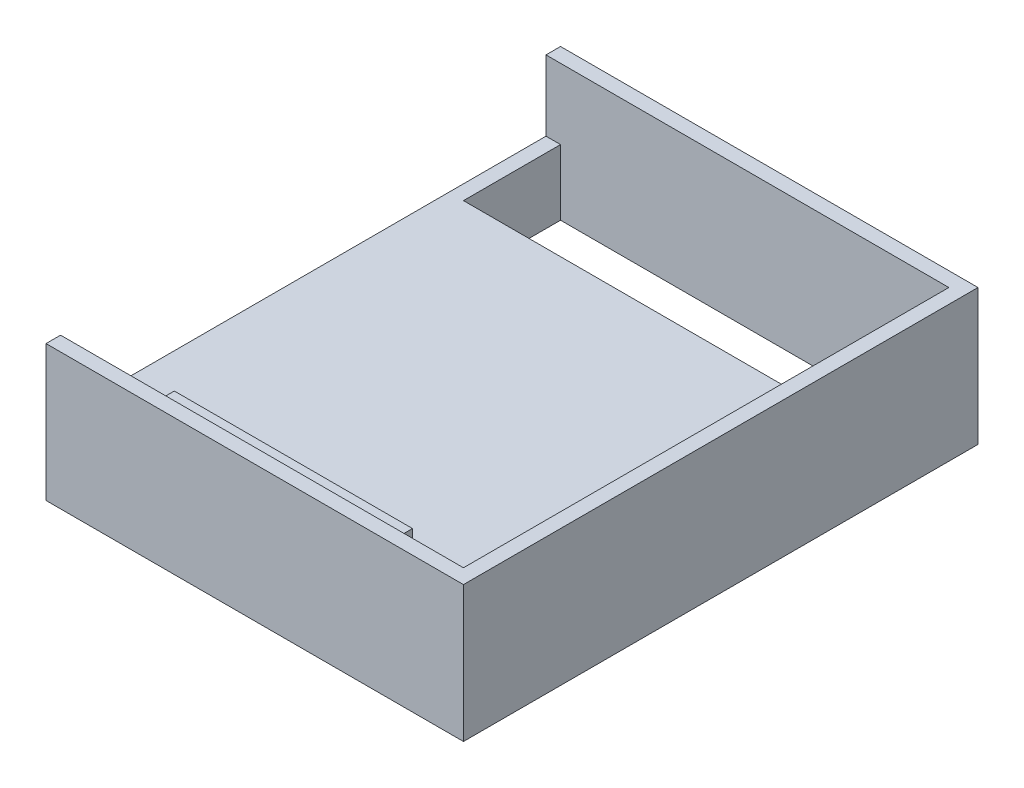
SolidWorks part; units mm, degrees
ref_plane "前视基准面" through (0, 0, 0) normal (0, 0, 1) x (1, 0, 0)
ref_plane "上视基准面" through (0, 0, 0) normal (0, 1, 0) x (1, 0, 0)
ref_plane "右视基准面" through (0, 0, 0) normal (1, 0, 0) x (0, 0, -1)
other "Configuration Table"
sketch "草图1" plane through (0, 0, 0) normal (0, 1, 0) x (1, 0, 0)
  line L0 (0, 0) -> (0, 42.4)
  line L1 (0, 42.4) -> (34.4, 42.4)
  line L2 (34.4, 0) -> (0, 0)
  line L3 (34.4, 42.4) -> (34.4, 0)
extrude "凸台-拉伸1" add sketch "草图1" along normal blind 7
sketch "草图2" plane through (0, 7, 0) normal (0, 1, 0) x (1, 0, 0)
  line L1 (0, 41.2) -> (33.2, 41.2)
  line L2 (33.2, 41.2) -> (33.2, 1.2)
  line L3 (33.2, 1.2) -> (0, 1.2)
  line L4 (0, 41.2) -> (0, 1.2)
extrude "切除-拉伸1" cut sketch "草图2" against normal blind 5.8
sketch "草图3" plane through (0, 0, 0) normal (0, -1, 0) x (1, 0, 0)
  line L1 (0, 0) -> (34.4, 0)
  line L2 (0, 0) -> (0, -42.4)
  line L3 (0, -42.4) -> (34.4, -42.4)
  line L4 (34.4, 0) -> (34.4, -42.4)
extrude "凸台-拉伸2" add sketch "草图3" along normal blind 4.2
sketch "草图4" plane through (0, -4.2, 0) normal (0, -1, 0) x (1, 0, 0)
  line L0 (1.2, -1.2) -> (1.2, -41.2)
  line L1 (1.2, -1.2) -> (33.2, -1.2)
  line L2 (33.2, -1.2) -> (33.2, -41.2)
  line L3 (33.2, -41.2) -> (1.2, -41.2)
extrude "切除-拉伸2" cut sketch "草图4" against normal blind 4.2
sketch "草图5" plane through (0, 0, 0) normal (0, -1, 0) x (1, 0, 0)
  line L0 (1.2, -41.2) -> (33.2, -41.2)
  line L1 (33.2, -41.2) -> (33.2, -33.2)
  line L2 (33.2, -41.2) -> (33.2, -1.2) construction
  line L3 (33.2, -33.2) -> (1.2, -33.2)
  line L4 (1.2, -1.2) -> (1.2, -41.2) construction
  line L5 (1.2, -33.2) -> (1.2, -41.2)
extrude "切除-拉伸-穿线孔" cut sketch "草图5" against normal blind 1.2
sketch "草图6" plane through (0, 1.2, 0) normal (0, 1, 0) x (1, 0, 0)
  line L1 (17.2, 1.2) -> (7.3727, 1.2)
  line L3 (0, 1.2) -> (33.2, 1.2) construction
  line L7 (0, 0) -> (34.4, 0) construction
  line L8 (0, 1.2) -> (33.2, 1.2) construction
  line L9 (7.3727, 1.2) -> (7.3727, 3.2)
  line L10 (17.2, 1.2) -> (27, 1.2)
  line L11 (27, 1.2) -> (27, 3.2)
  line L12 (7.3727, 3.2) -> (27, 3.2)
  point P0 (17.2, 1.2)
  point P9 (17.2, 0)
extrude "凸台-拉伸3" add sketch "草图6" along normal blind 4.5
